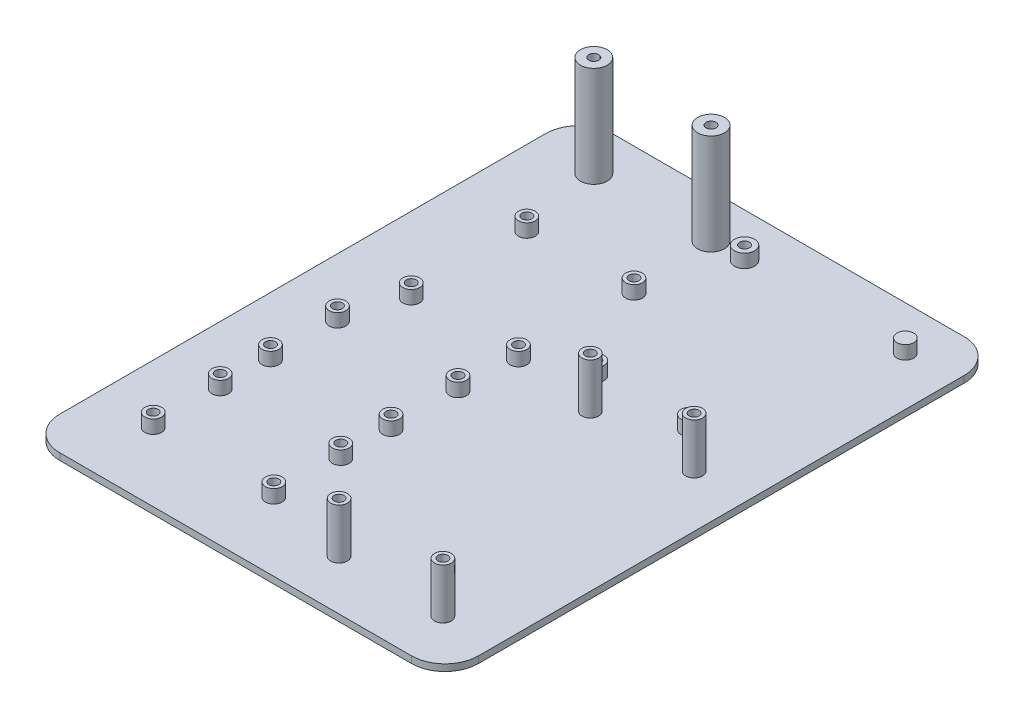
SolidWorks part; units mm, degrees
note: The reader was unsure of these and kept them because the rebuilt part matched: shared geometry of "草图1<3>", "草图1<4>".
ref_plane "前视基准面" through (0, 0, 0) normal (0, 0, 1) x (1, 0, 0)
ref_plane "上视基准面" through (0, 0, 0) normal (0, 1, 0) x (1, 0, 0)
ref_plane "右视基准面" through (0, 0, 0) normal (1, 0, 0) x (0, 0, -1)
sketch "草图1" plane through (0, 0, 0) normal (0, 1, 0) x (1, 0, 0)
  line L0 (-10, 0) -> (-45, 0)
  line L1 (0, 0) -> (48, 0) construction
  line L2 (0, 0) -> (0, -52) construction
  line L3 (0, -52) -> (48, -52) construction
  line L4 (48, 0) -> (48, -52) construction
  line L6 (-8, -25) -> (-40, -25) construction
  line L7 (-8, -25) -> (-8, -59.5) construction
  line L8 (-8, -59.5) -> (-40, -59.5) construction
  line L9 (-40, -25) -> (-40, -59.5) construction
  line L10 (46.9517, -62) -> (15.9517, -62) construction
  line L11 (46.9517, -62) -> (46.9517, -137) construction
  line L12 (46.9517, -137) -> (15.9517, -137) construction
  line L13 (15.9517, -62) -> (15.9517, -137) construction
  line L14 (-45.0483, -76.4828) -> (-9.0483, -76.4828) construction
  line L15 (-45.0483, -76.4828) -> (-45.0483, -96.4828) construction
  line L16 (-45.0483, -96.4828) -> (-9.0483, -96.4828) construction
  line L17 (-9.0483, -76.4828) -> (-9.0483, -96.4828) construction
  line L18 (-45.0483, -111.4828) -> (-9.0483, -111.4828) construction
  line L19 (-45.0483, -111.4828) -> (-45.0483, -131.4828) construction
  line L20 (-45.0483, -131.4828) -> (-9.0483, -131.4828) construction
  line L21 (-9.0483, -111.4828) -> (-9.0483, -131.4828) construction
  circle A0 centre (-45, 0) radius 4
  circle A1 centre (-10, 0) radius 4
  circle A2 centre (0, 0) radius 3
  circle A3 centre (48, 0) radius 2.5
  circle A4 centre (48, -52) radius 2.5
  circle A5 centre (0, -52) radius 2.5
  circle A6 centre (-40, -25) radius 2.5
  circle A7 centre (-8, -25) radius 2.5
  circle A8 centre (-8, -59.5) radius 2.5
  circle A9 centre (-40, -59.5) radius 2.5
  circle A10 centre (15.9517, -62) radius 2.5
  circle A11 centre (46.9517, -62) radius 2.5
  circle A12 centre (46.9517, -137) radius 2.5
  circle A13 centre (15.9517, -137) radius 2.5
  circle A14 centre (-45.0483, -76.4828) radius 2.5
  circle A15 centre (-9.0483, -76.4828) radius 2.5
  circle A16 centre (-9.0483, -96.4828) radius 2.5
  circle A17 centre (-45.0483, -96.4828) radius 2.5
  circle A18 centre (-9.0483, -131.4828) radius 2.5
  circle A19 centre (-9.0483, -111.4828) radius 2.5
  circle A20 centre (-45.0483, -111.4828) radius 2.5
  circle A21 centre (-45.0483, -131.4828) radius 2.5
  circle A22 centre (7.6, -52) radius 2.5
  circle A23 centre (35.5, -52) radius 2.5
  point P5 (7.6, -52)
  point P6 (35.5, -52)
  point P8 (0, 0)
  point P9 (48, 0)
  point P10 (0, -29.2277)
  dimension "D7" = 8
  dimension "D8" = 8
  dimension "D9" = 6
  dimension "D10" = 5
  dimension "D11" = 5
  dimension "D12" = 5
  dimension "D17" = 5
  dimension "D18" = 5
  dimension "D19" = 5
  dimension "D20" = 5
  dimension "D24" = 5
  dimension "D25" = 5
  dimension "D26" = 5
  dimension "D27" = 5
  dimension "D34" = 5
  dimension "D35" = 5
  dimension "D36" = 5
  dimension "D37" = 5
  dimension "D38" = 5
  dimension "D39" = 5
  dimension "D40" = 5
  dimension "D41" = 5
  dimension "D42" = 5
  dimension "D43" = 5
  dimension "D1" = 48
  dimension "D2" = 52
  dimension "D3" = 7.6
  dimension "D4" = 27.9
  dimension "D5" = 35
  dimension "D6" = 10
  dimension "D13" = 8
  dimension "D14" = 32
  dimension "D15" = 34.5
  dimension "D16" = 25
  dimension "D21" = 10
  dimension "D22" = 75
  dimension "D23" = 31
  dimension "D28" = 36
  dimension "D29" = 20
  dimension "D30" = 36
  dimension "D31" = 20
  dimension "D32" = 15
  dimension "D33" = 25
extrude "凸台-拉伸1" add sketch "草图1" along normal blind 4 contours A7 | A2 | A16 | A17 | A14 | A15 | A21 | A20 | A19 | A9 | A8 | A3 | A18 | A22 | A23 | A6
extrude "凸台-拉伸2" add sketch "草图1<3>" along normal blind 15 separate body contours A13 | A12 | A11 | A10
sketch "草图1<3>" plane through (0, 0, 0) normal (0, 1, 0) x (1, 0, 0) same geometry as "草图1"
extrude "凸台-拉伸3" add sketch "草图1<4>" along normal blind 30 separate body contours A0 | A1
sketch "草图1<4>" plane through (0, 0, 0) normal (0, 1, 0) x (1, 0, 0) same geometry as "草图1"
sketch "草图2" plane through (0, 0, 0) normal (0, 1, 0) x (1, 0, 0)
  line L1 (-62.5, 13.0742) -> (62.5, 13.0742)
  line L2 (-62.5, 13.0742) -> (-62.5, -151.9258)
  line L3 (-62.5, -151.9258) -> (62.5, -151.9258)
  line L4 (62.5, 13.0742) -> (62.5, -151.9258)
  line L5 (0, -151.9258) -> (0, 13.0742) construction
  line L6 (-62.5, -69.4258) -> (62.5, -69.4258) construction
  point P0 (0, -69.4258)
  dimension "D1" = 125
  dimension "D2" = 165
extrude "凸台-拉伸4" add sketch "草图2" against normal blind 2
fillet "圆角1" radius 10 4 edges at (-62.5, -1, 151.9258) (-62.5, -1, -13.0742) (62.5, -1, 151.9258) (62.5, -1, -13.0742)
sketch "草图5" plane through (0, 0, 0) normal (0, 1, 0) x (1, 0, 0)
  point P0 (0, 0)
  point P1 (-10, 0)
  point P3 (-45, 0)
  point P5 (-40, -25)
  point P7 (-8, -25)
  point P9 (48, 0)
  point P11 (35.5, -52)
  point P13 (-40, -59.5)
sketch "草图6" plane through (0, 0, 0) normal (0, 1, 0) x (1, 0, 0)
  point P0 (-8, -59.5)
  point P1 (7.6, -52)
  point P3 (15.9517, -62)
  point P5 (46.9517, -62)
  point P7 (-9.0483, -76.4828)
  point P9 (-45.0483, -76.4828)
  point P11 (-45.0483, -96.4828)
  point P13 (-9.0483, -96.4828)
  point P15 (-9.0483, -111.4828)
  point P17 (-45.0483, -111.4828)
  point P19 (-45.0483, -131.4828)
  point P21 (-9.0483, -131.4828)
  point P23 (15.9517, -137)
  point P25 (46.9517, -137)
hole_wizard "大小mm 暗销孔3" positions "3D草图5" profile "草图9" hole size "Ø3.0" standard "ANSI Metric"
sketch3d "3D草图5"
  line L0 (48, 4, 0) -> (48, 0, 0) construction
  line L1 (-8, 4, 25) -> (-8, 0, 25) construction
  point P0 (-40, 0, 59.5)
  point P3 (15.9517, 0, 62)
  point P7 (-45.0483, 0, 131.4828)
  point P10 (-45.0483, 0, 111.4828)
  point P13 (-45.0483, 0, 96.4828)
  point P16 (-45.0483, 0, 76.4828)
  point P19 (-40, 0, 25)
  point P22 (-45, 0, 0)
  point P25 (-10, 0, 0)
  point P28 (0, 0, 0)
  point P31 (48, 0, 0)
  point P36 (35.5, 0, 52)
  point P39 (46.9517, 0, 62)
  point P42 (46.9517, 0, 137)
  point P45 (15.9517, 0, 137)
  point P48 (-9.0483, 0, 131.4828)
  point P51 (-9.0483, 0, 111.4828)
  point P54 (-9.0483, 0, 96.4828)
  point P57 (-9.0483, 0, 76.4828)
  point P60 (-8, 0, 59.5)
  point P63 (7.6, 0, 52)
  point P66 (-8, 4, 25)
  point P70 (0, 0, 0)
  point P72 (0, 0, 0)
  point P75 (0, 0, 0)
  point P77 (0, 0, 0)
  point P79 (0, 0, 0)
  point P81 (-14.1299, 0, -25.3803)
sketch "草图9" plane through (-40, 0, 59.5) normal (1, 0, 0) x (0, 0, -1)
  line L0 (0, 0) -> (0, 30)
  line L1 (0, 30) -> (1.475, 30)
  line L2 (1.475, 30) -> (1.475, 0)
  line L5 (1.475, 0) -> (0, 0)
  line L11 (0, -6.35) -> (0, 107.95) construction
  dimension "通孔孔直径" = 2.95
  dimension "通孔孔深度" = 30
hole_wizard "大小mm 暗销孔3" positions "3D草图6" profile "草图10" hole size "Ø3.0" standard "ANSI Metric"
sketch3d "3D草图6"
  point P0 (-8, 0, 25)
  point P3 (0, 0, 0)
sketch "草图10" plane through (-8, 0, 25) normal (1, 0, 0) x (0, 0, -1)
  line L0 (0, 0) -> (0, 30)
  line L1 (0, 30) -> (1.475, 30)
  line L2 (1.475, 30) -> (1.475, 0.05)
  line L3 (1.475, 0.05) -> (1.525, 0)
  line L5 (1.525, 0) -> (0, 0)
  line L6 (-1.475, 0.05) -> (-1.525, 0) construction
  line L11 (0, -6.35) -> (0, 107.95) construction
  dimension "通孔孔直径" = 2.95
  dimension "通孔孔深度" = 30
  dimension "近端锥形沉头孔直径" = 3.05
  dimension "近端锥形沉头孔角度" = 90
